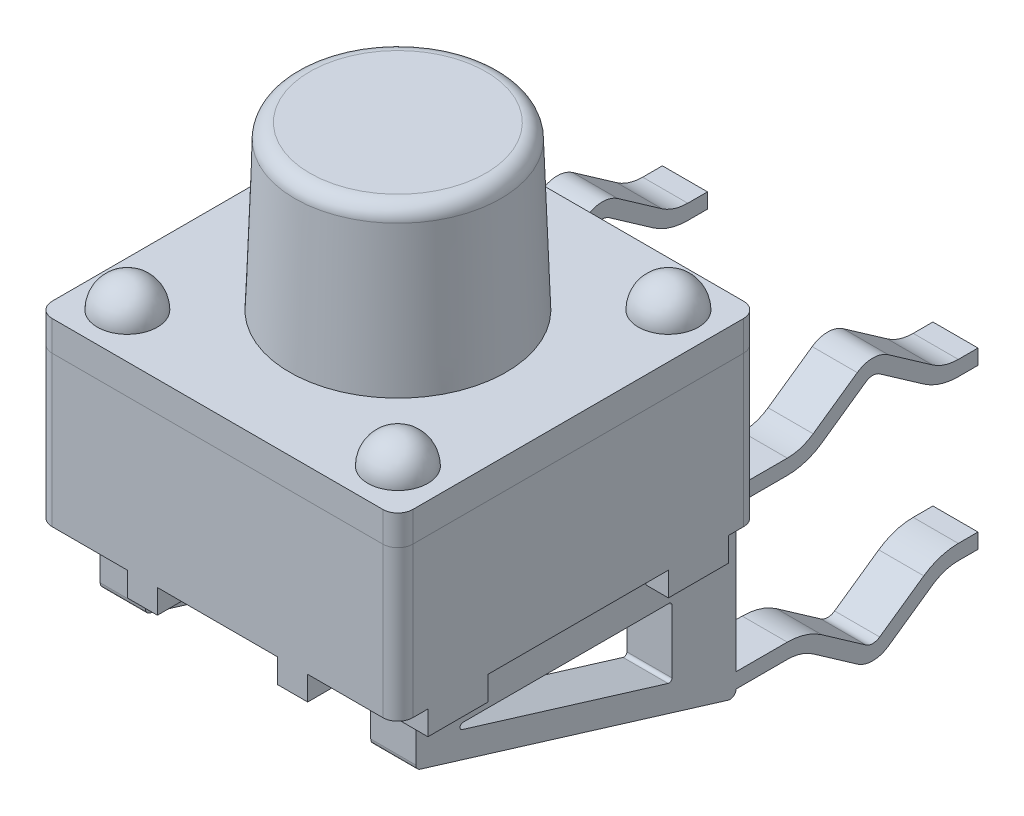
SolidWorks part; units mm, degrees
ref_plane "Front Plane" through (0, 0, 0) normal (0, 0, 1) x (1, 0, 0)
ref_plane "Top Plane" through (0, 0, 0) normal (0, 1, 0) x (1, 0, 0)
ref_plane "Right Plane" through (0, 0, 0) normal (1, 0, 0) x (0, 0, -1)
sketch "Sketch1" plane through (0, 0, 0) normal (0, 1, 0) x (1, 0, 0)
  line L1 (-3, -3) -> (3, -3)
  line L2 (-3, -3) -> (-3, 3)
  line L3 (-3, 3) -> (3, 3)
  line L4 (3, -3) -> (3, 3)
  line L5 (-3, -3) -> (3, 3) construction
  line L6 (-3, 3) -> (3, -3) construction
  point P0 (0, 0)
  dimension "D1" = 6
  dimension "D2" = 6
extrude "Extrude1" add sketch "Sketch1" along normal blind 3.4
sketch "Sketch2" plane through (0, 0, 0) normal (0, -1, 0) x (1, 0, 0)
  line L0 (-3, -3) -> (-3, 3) construction
  line L1 (-3, 1.5) -> (-1.5, 1.5)
  line L2 (-3, 1.5) -> (-3, -1.5)
  line L3 (-3, -1.5) -> (-1.5, -1.5)
  line L4 (-1.5, 1.5) -> (-1.5, -1.5)
  line L5 (3, -3) -> (-3, -3) construction
  line L6 (-3, -2.5) -> (-1.5, -2.5)
  line L7 (-3, -2.5) -> (-3, -3)
  line L8 (-3, -3) -> (-1.5, -3)
  line L9 (-1.5, -2.5) -> (-1.5, -3)
  line L10 (-3, 3) -> (3, 3) construction
  line L11 (-3, 3) -> (-1.5, 3)
  line L12 (-3, 3) -> (-3, 2.5)
  line L13 (-3, 2.5) -> (-1.5, 2.5)
  line L14 (-1.5, 3) -> (-1.5, 2.5)
  line L15 (1, 3) -> (-1, 3)
  line L16 (0, 3) -> (0, -3) construction
  line L17 (1, -3) -> (-1, -3)
  line L18 (-1, 3) -> (-1, -3)
  line L19 (0.5, -2) -> (0.5, -2.5)
  line L20 (0.5, 2.5) -> (-0.5, 2.5)
  line L21 (0.5, 0.25) -> (0.5, -0.25)
  line L22 (0.5, 2) -> (-0.5, 2)
  line L23 (-0.5, 2.5) -> (-0.5, 2)
  line L24 (0.5, 0.25) -> (-0.5, 0.25)
  line L25 (0.5, 2.5) -> (0.5, 2)
  line L26 (0.5, -0.25) -> (-0.5, -0.25)
  line L27 (-0.5, 0.25) -> (-0.5, -0.25)
  line L28 (0.5, -2) -> (-0.5, -2)
  line L29 (1, 3) -> (1, -3)
  line L30 (0.5, -2.5) -> (-0.5, -2.5)
  line L31 (-0.5, -2) -> (-0.5, -2.5)
  line L32 (1.5, 3) -> (1.5, 2.5)
  line L33 (3, 2.5) -> (1.5, 2.5)
  line L34 (3, 3) -> (3, 2.5)
  line L35 (3, 3) -> (1.5, 3)
  line L36 (1.5, -2.5) -> (1.5, -3)
  line L37 (3, -3) -> (1.5, -3)
  line L38 (3, -2.5) -> (3, -3)
  line L39 (3, -2.5) -> (1.5, -2.5)
  line L40 (1.5, 1.5) -> (1.5, -1.5)
  line L41 (3, -1.5) -> (1.5, -1.5)
  line L42 (3, 1.5) -> (3, -1.5)
  line L43 (3, 1.5) -> (1.5, 1.5)
  point P25 (0, 2.5)
  point P29 (0, 0.25)
  point P33 (0, -2)
  point P40 (0, -2.5)
  point P42 (0, -0.25)
  point P44 (0, 2)
  dimension "D1" = 3
  dimension "D2" = 1.5
  dimension "D3" = 0.5
  dimension "D4" = 1.5
  dimension "D5" = 1
  dimension "D6" = 0.5
  dimension "D7" = 0.5
  dimension "D8" = 0.25
extrude "Extrude2" cut sketch "Sketch2" against normal blind 0.4
sketch "Sketch3" plane through (0, 3.4, 0) normal (0, 1, 0) x (1, 0, 0)
  line L0 (-2.25, 1.75) -> (-2.25, 2.75)
  arc A0 (-2.25, 2.75) -> (-2.25, 1.75) centre (-2.25, 2.25) ccw
  dimension "D3" = 1
  dimension "D1" = 2.25
  dimension "D2" = 2.25
revolve "Revolve1" add sketch "Sketch3" angle 180 about L0
pattern_linear "LPattern1" count 2 spacing 4.5 along (1, 0, 0) count 2 spacing 4.5 along (0, 0, 1) of "Revolve1"
sketch "Sketch4" plane through (0, 3.4, 0) normal (0, 1, 0) x (1, 0, 0)
  circle A0 centre (0, 0) radius 1.8
  dimension "D1" = 3.6
extrude "Extrude3" add sketch "Sketch4" along normal blind 2.7 draft 2
ref_plane "Plane1" through (2.25, 0, 0) normal (1, 0, 0) x (0, 0, -1)
sketch "Sketch5" plane through (2.25, 0, 0) normal (1, 0, 0) x (0, 0, -1)
  line L0 (7.025, 0.4) -> (6.6971, 0.4)
  line L1 (6.1235, 0.5808) -> (5.3897, 1.0947)
  line L2 (5.1603, 1.0947) -> (4.4265, 0.5808)
  line L3 (3.8529, 0.4) -> (3, 0.4)
  line L4 (3, 3.4) -> (3, 0.4) construction
  line L5 (3, 0.65) -> (3, 0.4)
  line L6 (7.025, 0.65) -> (6.6971, 0.65)
  line L7 (6.2669, 0.7856) -> (5.5331, 1.2995)
  line L8 (5.0169, 1.2995) -> (4.2831, 0.7856)
  line L9 (3.8529, 0.65) -> (3, 0.65)
  line L12 (7.025, 0.4) -> (7.025, 0.65)
  arc A0 (4.4265, 0.5808) -> (3.8529, 0.4) centre (3.8529, 1.4) cw
  arc A1 (6.6971, 0.4) -> (6.1235, 0.5808) centre (6.6971, 1.4) cw
  arc A2 (5.3897, 1.0947) -> (5.1603, 1.0947) centre (5.275, 0.9308) ccw
  arc A4 (6.6971, 0.65) -> (6.2669, 0.7856) centre (6.6971, 1.4) cw
  arc A5 (5.5331, 1.2995) -> (5.0169, 1.2995) centre (5.275, 0.9308) ccw
  arc A6 (4.2831, 0.7856) -> (3.8529, 0.65) centre (3.8529, 1.4) cw
  point P16 (5.275, 1.175)
extrude "Extrude4" add sketch "Sketch5" along normal mid plane 0.75
ref_plane "Plane2" through (0, 2.9, 0) normal (0, 1, 0) x (-1, 0, 0)
mirror "Mirror1" about plane through (0, 0, 0) normal (1, 0, 0) of "Extrude4"
sketch "Sketch6" plane through (0, 0, 0) normal (1, 0, 0) x (0, 0, -1)
  line L0 (-2.326, 0.6964) -> (-2.326, -0.6823)
  line L1 (-2.2553, -0.7779) -> (2.8707, -2.3462)
  line L3 (3, -2.0005) -> (3, 0.6964)
  line L4 (3, 3.4) -> (3, 0.4) construction
  line L5 (3, 0.6964) -> (-2.326, 0.6964)
  line L6 (3.8529, -2.0005) -> (3, -2.0005)
  line L7 (-1.5557, -0.5565) -> (1.87, -1.6045)
  line L8 (1.9347, -1.5567) -> (1.9347, -0.5087)
  line L9 (1.8847, -0.4587) -> (-1.5411, -0.4587)
  line L10 (7.025, -2.0005) -> (7.025, -2.2505)
  line L11 (3.8529, -2.2505) -> (3, -2.2505)
  line L12 (5.0169, -2.9) -> (4.2831, -2.3862)
  line L13 (6.2669, -2.3862) -> (5.5331, -2.9)
  line L14 (7.025, -2.2505) -> (6.6971, -2.2505)
  line L15 (5.1603, -2.6952) -> (4.4265, -2.1814)
  line L16 (6.1235, -2.1814) -> (5.3897, -2.6952)
  line L17 (7.025, -2.0005) -> (6.6971, -2.0005)
  arc A0 (1.87, -1.6045) -> (1.9347, -1.5567) centre (1.8847, -1.5567) ccw
  arc A1 (1.9347, -0.5087) -> (1.8847, -0.4587) centre (1.8847, -0.5087) ccw
  arc A2 (-1.5557, -0.5565) -> (-1.5411, -0.4587) centre (-1.5411, -0.5087) cw
  arc A3 (-2.326, -0.6823) -> (-2.2553, -0.7779) centre (-2.226, -0.6823) ccw
  arc A4 (2.8707, -2.3462) -> (3, -2.2505) centre (2.9, -2.2505) ccw
  arc A5 (4.2831, -2.3862) -> (3.8529, -2.2505) centre (3.8529, -3.0005) ccw
  arc A6 (5.5331, -2.9) -> (5.0169, -2.9) centre (5.275, -2.5314) cw
  arc A7 (6.6971, -2.2505) -> (6.2669, -2.3862) centre (6.6971, -3.0005) ccw
  arc A8 (5.3897, -2.6952) -> (5.1603, -2.6952) centre (5.275, -2.5314) cw
  arc A9 (6.6971, -2.0005) -> (6.1235, -2.1814) centre (6.6971, -3.0005) ccw
  arc A10 (4.4265, -2.1814) -> (3.8529, -2.0005) centre (3.8529, -3.0005) ccw
  dimension "D1" = 0.05
  dimension "D2" = 0.1
extrude "Boss-Extrude1" add sketch "Sketch6" along normal up to vertex (2.625 mm away) from vertex up to point (2.625, 0.4, -3) starting at point (1.875, 0.4, -3)
extrude "Boss-Extrude2" add sketch "Sketch6<2>" against normal up to vertex (2.625 mm away) from vertex up to point (-2.625, 0.4, -7.025) starting at point (-1.875, 0.4, -3)
sketch "Sketch6<2>" plane through (0, 0, 0) normal (1, 0, 0) x (0, 0, -1) same geometry as "Sketch6"
split line "Split Line1"
fillet "Fillet1" radius 0.25 9 edges at (-3, 3.15, -3) (3, 3.15, -3) (3, 3.15, 3) (-3, 3.15, 3) (-3, 1.65, -3) (3, 1.65, -3) (3, 1.65, 3) (-3, 1.65, 3) (0, 6.1, 1.7057)
scale "Масштаб1" scale about centroid uniform scaling yes scale factor 0.75
